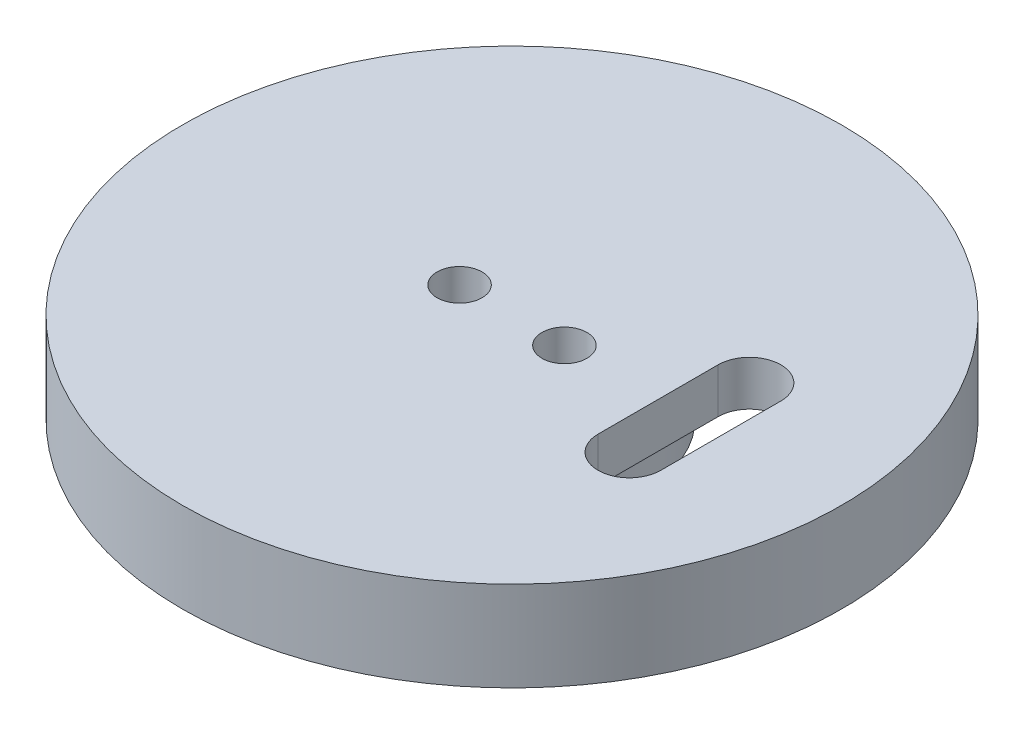
SolidWorks part; units mm, degrees
ref_plane "Plan de face" through (0, 0, 0) normal (0, 0, 1) x (1, 0, 0)
ref_plane "Plan de dessus" through (0, 0, 0) normal (0, 1, 0) x (1, 0, 0)
ref_plane "Plan de droite" through (0, 0, 0) normal (1, 0, 0) x (0, 0, -1)
sketch "Esquisse1" plane through (0, 0, 0) normal (0, 1, 0) x (1, 0, 0)
  line L0 (-3.5, 0) -> (3.5, 0) construction
  circle A0 centre (0, 0) radius 22
  circle A2 centre (-3.5, 0) radius 1.5
  circle A3 centre (3.5, 0) radius 1.5
  circle A15 centre (0, 0) radius 18 construction
  dimension "D1" = 44
  dimension "D2" = 36
  dimension "D3" = 3.5
  dimension "D4" = 7
  dimension "D5" = 3
  dimension "D6" = 3
extrude "Boss.-Extru.1" add sketch "Esquisse1" along normal blind 6
sketch "Esquisse2" plane through (0, 0, 0) normal (0, -1, 0) x (1, 0, 0)
  circle A0 centre (0, 0) radius 16.25
  circle A1 centre (0, 0) radius 8.65
  dimension "D1" = 32.5
  dimension "D2" = 17.3
extrude "Enlèv. mat.-Extru.1" cut sketch "Esquisse2" against normal blind 3
sketch "Esquisse3" plane through (0, 3, 0) normal (0, -1, 0) x (-1, 0, 0)
  line L0 (-11.8461, -4.0087) -> (-11.8461, 4.0087) construction
  line L1 (-13.9406, -4.0087) -> (-13.9406, 4.0087)
  line L2 (-9.7517, -4.0087) -> (-9.7517, 4.0087)
  line L3 (0, 0) -> (-15.8195, 0) construction
  arc A0 (-13.9406, -4.0087) -> (-9.7517, -4.0087) centre (-11.8461, -4.0087) ccw
  arc A1 (-9.7517, 4.0087) -> (-13.9406, 4.0087) centre (-11.8461, 4.0087) ccw
  point P2 (-11.8461, 0)
  point P10 (-11.9881, 0)
  point P11 (-11.6333, 0)
  point P12 (-13.2652, -5.002)
  point P13 (-11.7397, -4.328)
  point P14 (-11.8461, -4.0087)
extrude "Enlèv. mat.-Extru.2" cut sketch "Esquisse3" against normal blind 3
